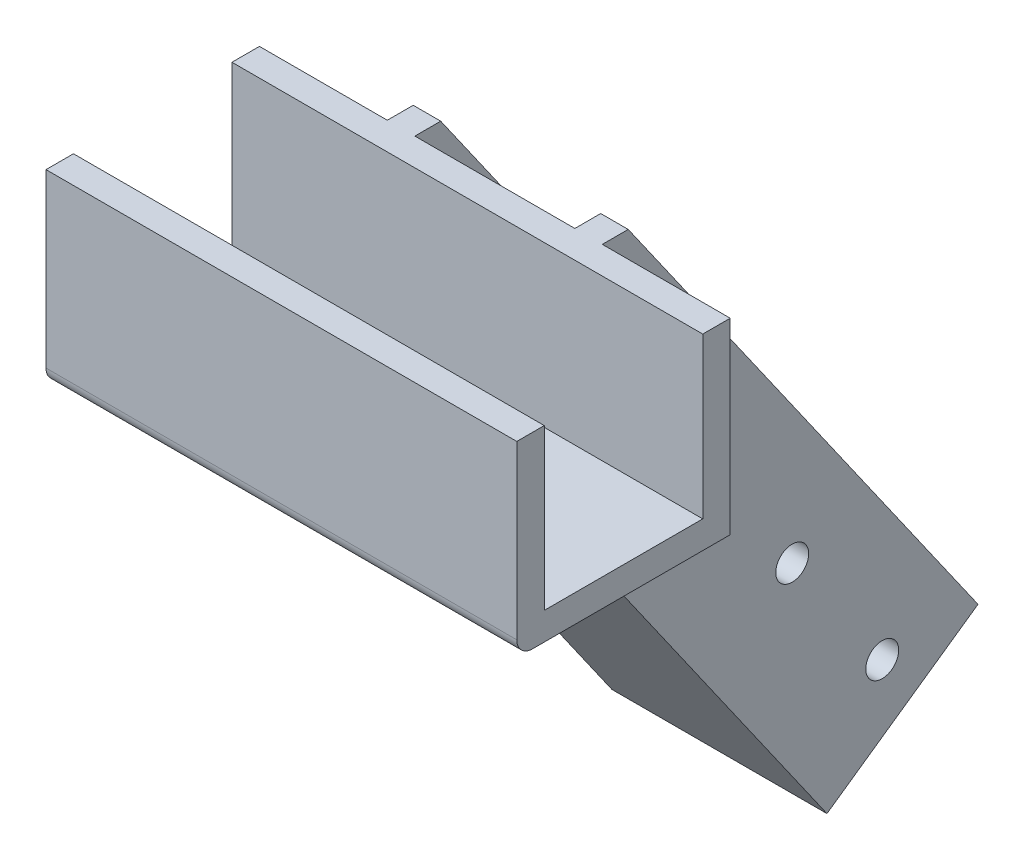
SolidWorks part; units mm, degrees
material "Custom Plastic"
ref_plane "Front Plane" through (0, 0, 0) normal (0, 0, 1) x (1, 0, 0)
ref_plane "Top Plane" through (0, 0, 0) normal (0, 1, 0) x (1, 0, 0)
ref_plane "Right Plane" through (0, 0, 0) normal (1, 0, 0) x (0, 0, -1)
sketch "Sketch1" plane through (0, 0, 0) normal (1, 0, 0) x (0, 0, -1)
  line L1 (-13.6, -11.95) -> (13.6, -11.95)
  line L2 (-13.6, -11.95) -> (-13.6, 11.95)
  line L3 (-13.6, 11.95) -> (13.6, 11.95)
  line L4 (13.6, -11.95) -> (13.6, 11.95)
  line L5 (-13.6, -11.95) -> (13.6, 11.95) construction
  line L6 (-13.6, 11.95) -> (13.6, -11.95) construction
  point P0 (0, 0)
  dimension "D1" = 27.2
  dimension "D2" = 23.9
extrude "Boss-Extrude1" add sketch "Sketch1" along normal mid plane 60
shell "Shell1" thickness 3.5 removed face at (30, 0, 0) removed face at (-30, 0, 0) removed face at (0, 11.95, 0)
sketch "Sketch2" plane through (0, 0, 0) normal (1, 0, 0) x (0, 0, -1)
  line L0 (4.9468, -11.95) -> (42.2292, -65.1949)
  line L2 (42.2292, -65.1949) -> (61.4793, -51.7158)
  line L3 (61.4793, -51.7158) -> (13.6, 16.6629)
  line L4 (13.6, -11.95) -> (13.6, 11.95) construction
  line L5 (-13.6, -11.95) -> (13.6, -11.95) construction
  line L6 (-13.6, 11.95) -> (-13.6, -11.95) construction
  line L7 (4.9468, -11.95) -> (13.6, -11.95)
  line L8 (13.6, -11.95) -> (13.6, 11.95)
  line L9 (13.6, 16.6629) -> (10.1, 16.6629)
  line L10 (10.1, 16.6629) -> (10.1, 11.95)
  line L11 (10.1, 11.95) -> (13.6, 11.95)
  point P4 (12.6234, 18.0577)
  dimension "D1" = 145
  dimension "D2" = 23.5
  dimension "D3" = 18.5468
  dimension "D4" = 65
extrude "Boss-Extrude2" add sketch "Sketch2" along normal mid plane 27.4
shell "Shell3" thickness 3.5054 removed face at (0, -58.4554, -51.8543) removed face at (0, -17.5265, -37.5396)
fillet "Fillet2" radius 2 1 edges at (0, -11.95, 13.6)
sketch "Sketch3" plane through (13.7, 0, 0) normal (1, 0, 0) x (0, 0, -1)
  line L0 (53.2878, -57.4516) -> (13.6, -0.7716) construction
  line L1 (42.2292, -65.1949) -> (61.4793, -51.7158) construction
  line L3 (61.4793, -51.7158) -> (13.6, 16.6629) construction
  line L4 (13.6, 11.95) -> (13.6, -11.95) construction
  circle A0 centre (49.2727, -51.7175) radius 2.1
  circle A1 centre (37.8012, -35.3345) radius 2.1
  circle A2 centre (26.3297, -18.9515) radius 2.1
  point P4 (13.6, -7.8701)
  point P11 (0, 0)
  dimension "D2" = 4.2
  dimension "D3" = 7
  dimension "D1" = 10
  dimension "D4" = 3
extrude "Cut-Extrude1" cut sketch "Sketch3" against normal through all
fillet "Fillet3" radius 10 1 edges at (0, -11.95, -4.9468)
sketch "Sketch4" plane through (0, 0, -10.1) normal (0, 0, 1) x (1, 0, 0)
  line L1 (-13.7, 16.6629) -> (13.7, 16.6629)
  line L2 (-13.7, 16.6629) -> (-13.7, 11.95)
  line L3 (-13.7, 11.95) -> (13.7, 11.95)
  line L4 (13.7, 16.6629) -> (13.7, 11.95)
extrude "Cut-Extrude2" cut sketch "Sketch4" against normal through all
